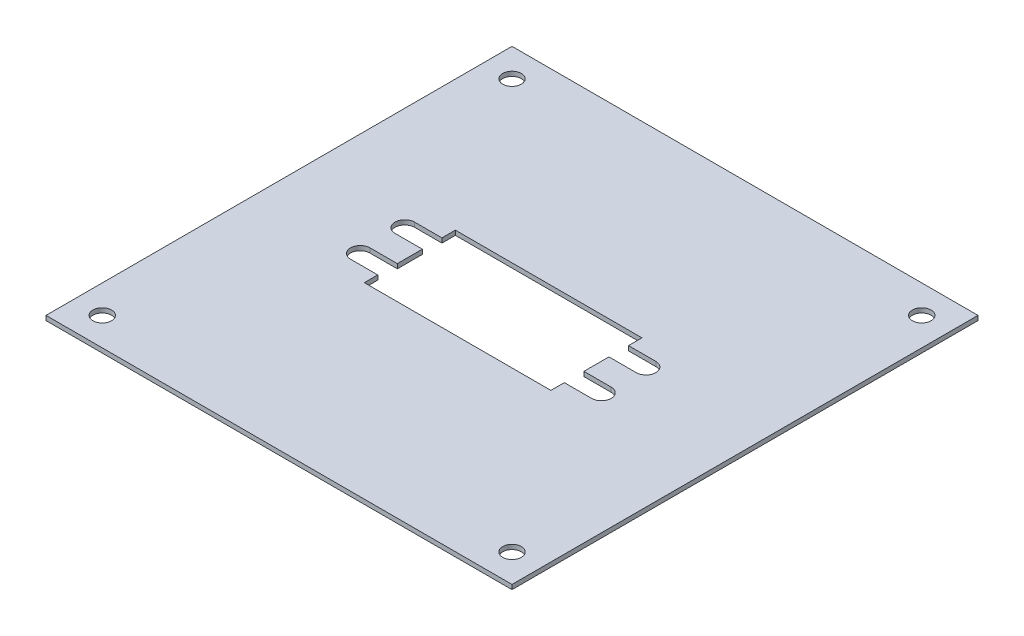
SolidWorks part; units mm, degrees
ref_plane "Front Plane" through (0, 0, 0) normal (0, 0, 1) x (1, 0, 0)
ref_plane "Top Plane" through (0, 0, 0) normal (0, 1, 0) x (1, 0, 0)
ref_plane "Right Plane" through (0, 0, 0) normal (1, 0, 0) x (0, 0, -1)
sketch "Sketch1" plane through (0, 0, 0) normal (0, 1, 0) x (1, 0, 0)
  line L0 (-51.2, 0) -> (51.2, 0) construction
  line L1 (-51.2, -51.2) -> (51.2, -51.2)
  line L2 (-51.2, -51.2) -> (-51.2, 51.2)
  line L3 (-51.2, 51.2) -> (51.2, 51.2)
  line L4 (51.2, -51.2) -> (51.2, 51.2)
  line L5 (-51.2, -51.2) -> (51.2, 51.2) construction
  line L6 (-51.2, 51.2) -> (51.2, -51.2) construction
  line L7 (0, 51.2) -> (0, -51.2) construction
  line L9 (-22.45, -10) -> (18.55, -10)
  line L10 (-22.45, -10) -> (-22.45, 10)
  line L11 (-22.45, 10) -> (18.55, 10)
  line L12 (18.55, -10) -> (18.55, 10)
  line L13 (-22.45, -10) -> (18.55, 10) construction
  line L14 (-22.45, 10) -> (18.55, -10) construction
  circle A0 centre (45.02, 45.02) radius 2.05
  circle A1 centre (45.02, -45.02) radius 2.05
  circle A2 centre (-45.02, -45.02) radius 2.05
  circle A3 centre (-45.02, 45.02) radius 2.05
  point P0 (0, 0)
  point P18 (-1.95, 0)
  dimension "D4" = 4.1
  dimension "D5" = 4.1
  dimension "D6" = 4.1
  dimension "D7" = 4.1
  dimension "D1" = 102.4
  dimension "D2" = 102.4
  dimension "D3" = 6.18
  dimension "D8" = 6.18
  dimension "D9" = 6.18
  dimension "D10" = 6.18
  dimension "D11" = 41
  dimension "D12" = 20
  dimension "D13" = 49.25
base flange "Base-Flange1" sketch "Sketch1" thickness 1 reverse thickness direction no parameters "D1"=0.6
sketch "Sketch7" plane through (0, 0, 0) normal (0, 1, 0) x (1, 0, 0)
  line L0 (-28.45, 4.9) -> (-16.45, 4.9) construction
  line L1 (-22.45, 10) -> (-22.45, -10) construction
  line L2 (-28.45, 7.05) -> (-16.45, 7.05)
  line L3 (-28.45, 2.75) -> (-16.45, 2.75)
  line L4 (-28.45, -4.9) -> (-16.45, -4.9) construction
  line L5 (-28.45, -2.75) -> (-16.45, -2.75)
  line L6 (-28.45, -7.05) -> (-16.45, -7.05)
  line L7 (12.55, 4.9) -> (24.55, 4.9) construction
  line L8 (18.55, -10) -> (18.55, 10) construction
  line L9 (12.55, 7.05) -> (24.55, 7.05)
  line L10 (12.55, 2.75) -> (24.55, 2.75)
  line L11 (12.55, -4.9) -> (24.55, -4.9) construction
  line L12 (12.55, -2.75) -> (24.55, -2.75)
  line L13 (12.55, -7.05) -> (24.55, -7.05)
  arc A0 (-28.45, 7.05) -> (-28.45, 2.75) centre (-28.45, 4.9) ccw
  arc A1 (-16.45, 2.75) -> (-16.45, 7.05) centre (-16.45, 4.9) ccw
  arc A2 (-28.45, -2.75) -> (-28.45, -7.05) centre (-28.45, -4.9) ccw
  arc A3 (-16.45, -7.05) -> (-16.45, -2.75) centre (-16.45, -4.9) ccw
  arc A4 (12.55, 7.05) -> (12.55, 2.75) centre (12.55, 4.9) ccw
  arc A5 (24.55, 2.75) -> (24.55, 7.05) centre (24.55, 4.9) ccw
  arc A6 (12.55, -2.75) -> (12.55, -7.05) centre (12.55, -4.9) ccw
  arc A7 (24.55, -7.05) -> (24.55, -2.75) centre (24.55, -4.9) ccw
  point P4 (-22.45, 4.9)
  point P12 (-22.45, -4.9)
  point P21 (18.55, 4.9)
  point P28 (18.55, -4.9)
  dimension "D1" = 4.3
  dimension "D2" = 12
  dimension "D3" = 4.9
  dimension "D4" = 4.3
  dimension "D5" = 12
  dimension "D6" = 4.9
  dimension "D7" = 4.3
  dimension "D8" = 12
  dimension "D9" = 4.3
  dimension "D10" = 12
extrude "Cut-Extrude2" cut sketch "Sketch7" against normal blind 10 normal cut yes
sketch "Bend-Lines1" plane through (0, 0, 0) normal (0, 1, 0) x (1, 0, 0)
sketch "Bounding-Box1" plane through (0, 0, 0) normal (0, 1, 0) x (1, 0, 0)
sheet metal parameters "Sheet-Metal(1)" thickness 1 parameters "D1"=0.6
flat pattern "Flat-Pattern(1)" [suppressed]
sketch "Bend-Lines2" plane through (0, 0, 0) normal (0, 1, 0) x (1, 0, 0)
sketch "Bounding-Box2" [suppressed] plane through (0, 0, 0) normal (0, 1, 0) x (1, 0, 0)
sheet metal parameters "Sheet-Metal(3)" thickness 1 parameters "D1"=0.6
flat pattern "Flat-Pattern(1)"
sketch "Bend-Lines2" plane through (0, 0, 0) normal (0, 1, 0) x (1, 0, 0)
sketch "Bounding-Box2" [suppressed] plane through (0, 0, 0) normal (0, 1, 0) x (1, 0, 0)
